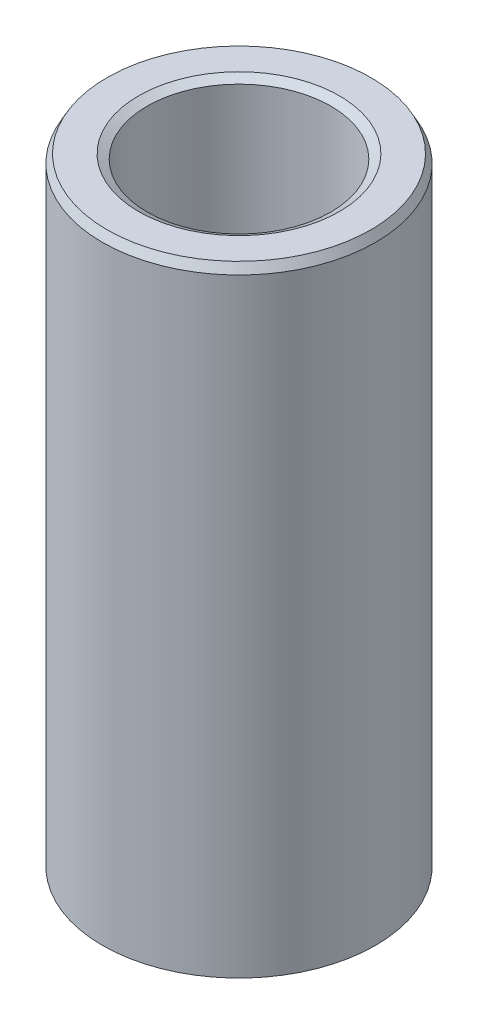
SolidWorks part; units mm, degrees
ref_plane "Front Plane" through (0, 0, 0) normal (0, 0, 1) x (1, 0, 0)
ref_plane "Top Plane" through (0, 0, 0) normal (0, 1, 0) x (1, 0, 0)
ref_plane "Right Plane" through (0, 0, 0) normal (1, 0, 0) x (0, 0, -1)
sketch "Sketch1" plane through (0, 0, 0) normal (0, 1, 0) x (1, 0, 0)
  circle A0 centre (0, 0) radius 35
  dimension "SLEEVE_OD" = 70
extrude "Boss-Extrude1" add sketch "Sketch1" along normal blind 159.4405
sketch "Sketch2" plane through (0, 0, 0) normal (0, 1, 0) x (1, 0, 0)
  circle A0 centre (0, 0) radius 23.5352
  dimension "BORE_D" = 47.0704
extrude "Cut-Extrude1" cut sketch "Sketch2" along normal through all
chamfer "Chamfer1" distance 2.1868 angle 28.711 4 edges at (0, 159.4405, 23.5352) (0, 0, 23.5352) (0, 0, 35) (0, 159.4405, 35) first distance on face at (0, 159.4405, 23.5352) first distance on face at (0, 0, 23.5352) first distance on face at (0, 159.4405, 35)
